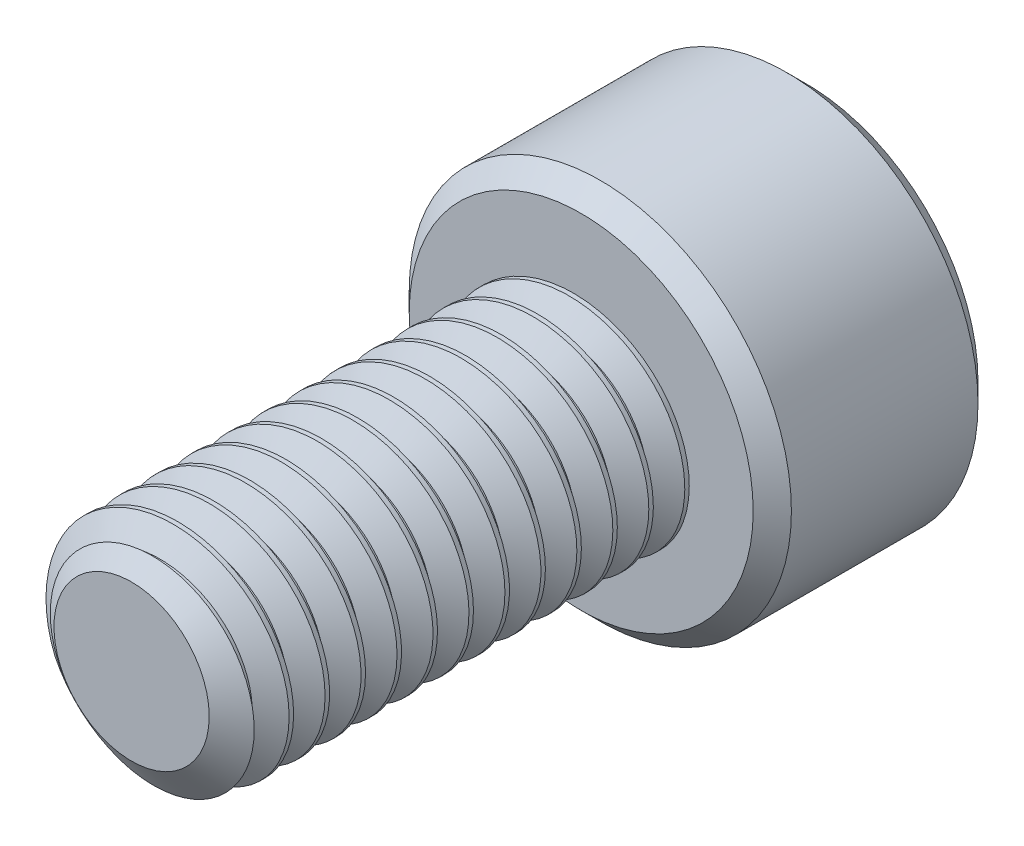
SolidWorks part; units mm, degrees
other "DetailItem1"
ref_plane "Front Plane" through (0, 0, 0) normal (0, 0, 1) x (1, 0, 0)
ref_plane "Top Plane" through (0, 0, 0) normal (0, 1, 0) x (1, 0, 0)
ref_plane "Right Plane" through (0, 0, 0) normal (1, 0, 0) x (0, 0, -1)
sketch "Sketch1" plane through (0, 0, 0) normal (0, 0, 1) x (1, 0, 0)
  circle A0 centre (0, 0) radius 2.5
  dimension "OD" = 5
extrude "Extrude1" add sketch "Sketch1" against normal blind 10
sketch "Sketch2" plane through (0, 0, 0) normal (0, 0, 1) x (1, 0, 0)
  circle A0 centre (0, 0) radius 2.5 construction
  circle A1 centre (0, 0) radius 2.5
curve "Helix/Spiral1" pitch 0.8 height 10.8 turns 13.5 parameters "pitch"=0.8
sketch "Sketch3" plane through (0, 0, 0) normal (1, 0, 0) x (0, 0, -1)
  line L0 (-0.7, 2.5) -> (-0.4, 1.9804)
  line L1 (-0.4, 1.9804) -> (-0.3, 1.9804)
  line L2 (-0.3, 1.9804) -> (0, 2.5)
  line L3 (-0.7, 2.5) -> (0, 2.5)
  line L4 (-0.35, 2.5) -> (-0.35, 1.9804) construction
  line L5 (-0.55, 2.2402) -> (-0.15, 2.2402) construction
  line L6 (0, 2.5) -> (0, -2.5) construction
  dimension "D1" = 0.1
  dimension "D2" = 0.4
  dimension "D3" = 60
sweep "Cut-Sweep1" cut profiles "Sketch3" path "Helix/Spiral1"
sketch "Sketch4" plane through (0, 0, 0) normal (1, 0, 0) x (0, 0, -1)
  line L0 (0.5417, 2.5) -> (0, 1.7264)
  line L1 (0, 1.7264) -> (0, 2.5)
  line L2 (0.5417, 2.5) -> (0, 2.5)
  line L3 (-0.7, 2.5) -> (0, 2.5) construction
  line L4 (0, 0) -> (7.0209, 0) construction
  dimension "D1" = 55
  dimension "D2" = 0.254
revolve "Cut-Revolve1" cut sketch "Sketch4" angle 360 about L4
sketch "Sketch6" plane through (0, 0, -10) normal (0, 0, -1) x (-1, 0, 0)
  circle A0 centre (0, 0) radius 4.25
  dimension "head dia" = 8.5
extrude "Extrude2" add sketch "Sketch6" along normal blind 5
sketch "Sketch7" plane through (0, 0, -15) normal (0, 0, -1) x (-1, 0, 0)
  line L1 (0, 2.3094) -> (-2, 1.1547)
  line L2 (-2, 1.1547) -> (-2, -1.1547)
  line L3 (-2, -1.1547) -> (0, -2.3094)
  line L4 (0, -2.3094) -> (2, -1.1547)
  line L5 (2, -1.1547) -> (2, 1.1547)
  line L6 (2, 1.1547) -> (0, 2.3094)
  circle A0 centre (0, 0) radius 2 construction
  dimension "hex dia" = 4
extrude "Cut-Extrude1" cut sketch "Sketch7" against normal blind 3
sketch "Sketch8" plane through (0, 0, -15) normal (0, 0, -1) x (-1, 0, 0)
  circle A0 centre (0, 0) radius 2.3094
extrude "Cut-Extrude2" cut sketch "Sketch8" against normal through all draft 45
chamfer "Chamfer1" distance 0.425 angle 45 2 edges at (-4.25, 0, -15) (-4.25, 0, -10)
sketch "Sketch10" plane through (0, 0, -10) normal (0, 0, 1) x (1, 0, 0)
  circle A1 centre (0, 0) radius 2.5
  circle A2 centre (0, 0) radius 2.5
  dimension "D1" = 0
ref_plane "Plane1" through (0, 0, 0) normal (0, 0, 1) x (1, 0, 0)
extrude "partial thread" [suppressed] add sketch "Sketch10" along normal up to surface (13 mm away) separate body
chamfer "Chamfer2" [suppressed] distance 0.1 angle 45
combine bodies "Combine1" [suppressed] operation type add bodies to combine 107 108
sketch "Sketch9" plane through (0, 0, 0) normal (1, 0, 0) x (0, 0, -1)
  line L0 (0, 2.5) -> (0, -2.5) construction
  line L1 (2, 2.5) -> (2, -2.5) construction
  dimension "D1" = 2
equation "\"D3@Helix/Spiral1\" = \"screw length@Extrude1\"+\"pitch@Helix/Spiral1\""
equation "\"D1@Sketch3\" = \"pitch@Helix/Spiral1\"*.125"
equation "\"D2@Sketch3\" = \"pitch@Helix/Spiral1\"*.5"
equation "\"D1@Cut-Extrude1\" = \"hex dia@Sketch7\"*.75"
equation "\"D1@Chamfer1\" = \"head dia@Sketch6\"*.05"
equation "\"D1@Sketch9\" = \"pitch@Helix/Spiral1\"*2.5"
equation "\"D1@Chamfer2\"=\"OD@Sketch1\"*.02"
